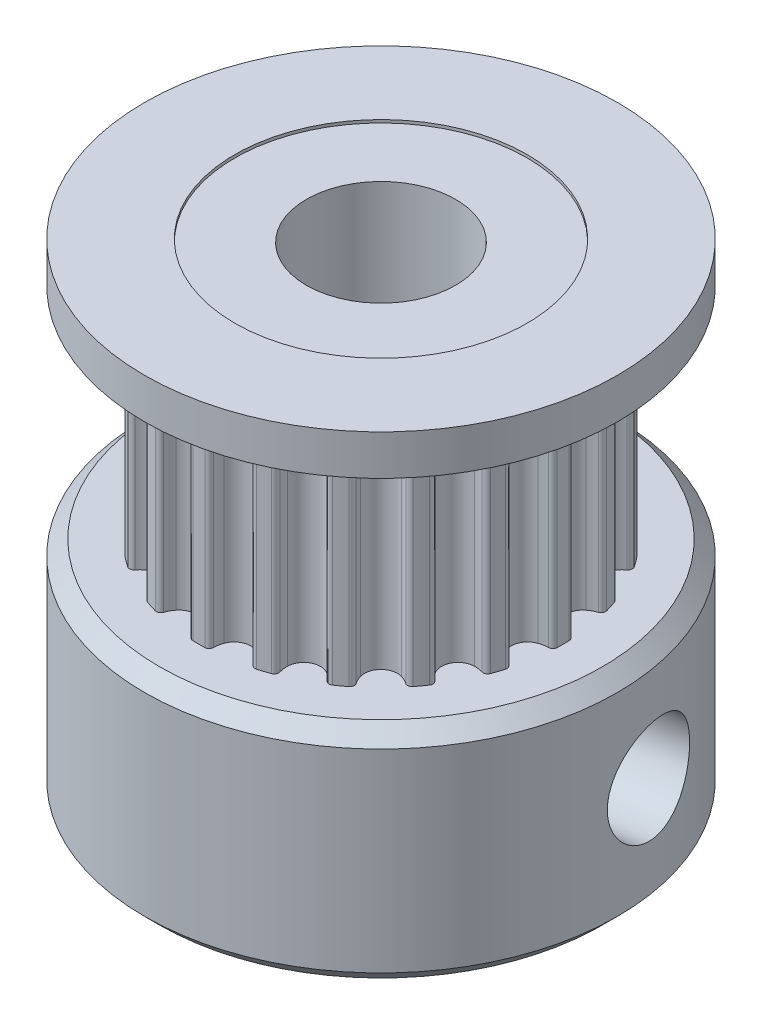
SolidWorks part; units mm, degrees
ref_plane "Front Plane" through (0, 0, 0) normal (0, 0, 1) x (1, 0, 0)
ref_plane "Top Plane" through (0, 0, 0) normal (0, 1, 0) x (1, 0, 0)
ref_plane "Right Plane" through (0, 0, 0) normal (1, 0, 0) x (0, 0, -1)
sketch "Sketch1" plane through (0, 0, 0) normal (0, 1, 0) x (1, 0, 0)
  circle A0 centre (0, 0) radius 6.3662
  dimension "D1" = 12.7324
extrude "Boss-Extrude1" add sketch "Sketch1" along normal mid plane 7.36
sketch "Sketch2" plane through (0, 0, 0) normal (0, 1, 0) x (1, 0, 0)
  line L0 (0, 0) -> (0, 6.1122) construction
  line L1 (0, 0) -> (0.9257, 5.8443) construction
  line L2 (0, 6.1122) -> (0, 6.3662)
  line L3 (0.9257, 5.8443) -> (0.9959, 6.2878) construction
  line L4 (0.9959, 6.2878) -> (1.3888, 6.2129) construction
  line L5 (1.3888, 6.2129) -> (1.3462, 5.9897) construction
  line L6 (1.8888, 5.813) -> (1.9673, 6.0546)
  arc A1 (0, 6.1122) -> (0.2016, 6.1089) centre (0, 0) cw
  arc A2 (0.2016, 6.1089) -> (0.3466, 5.963) centre (0.1967, 5.959) cw
  arc A3 (0.3466, 5.963) -> (0.4011, 5.663) centre (1.3462, 5.9897) ccw
  arc A4 (0.4011, 5.663) -> (1.3685, 5.5098) centre (0.9257, 5.8443) ccw
  circle A5 centre (0, 0) radius 6.3662 construction
  arc A6 (0, 6.3662) -> (1.9673, 6.0546) centre (0, 0) cw
  arc A7 (1.513, 5.7782) -> (1.3685, 5.5098) centre (0.5706, 6.1126) cw
  arc A8 (1.696, 5.8722) -> (1.513, 5.7782) centre (1.6544, 5.7281) ccw
  arc A9 (1.8888, 5.813) -> (1.696, 5.8722) centre (0, 0) ccw
  dimension "D2" = 0.15
  dimension "D3" = 1
  dimension "D4" = 0.555
  dimension "D1" = 9
  dimension "D5" = 0.254
  dimension "D6" = 0.4
  dimension "D7" = 1.004
extrude "Cut-Extrude1" cut sketch "Sketch2" against normal through all both and the other way through all
pattern_circular "CirPattern1" count 20 over 360 about axis through (0, 3.68, 0) along (0, -1, 0) of "Cut-Extrude1"
sketch "Sketch3" plane through (0, 0, 0) normal (0, 1, 0) x (1, 0, 0)
  circle A0 centre (0, 0) radius 7.925
  dimension "15.85" = 15.85
extrude "Boss-Extrude2" add sketch "Sketch3" along normal blind 1.35 from surface starting at face at (0, 3.68, 0)
extrude "Boss-Extrude3" add sketch "Sketch3<2>" against normal blind 7.5 from surface starting at face at (0, -3.68, 0)
sketch "Sketch3<2>" plane through (0, 0, 0) normal (0, 1, 0) x (1, 0, 0) same geometry as "Sketch3"
sketch "Sketch4" plane through (0, 0, 0) normal (0, 1, 0) x (1, 0, 0)
  circle A0 centre (0, 0) radius 2.5
  dimension "D1" = 5
extrude "Cut-Extrude2" cut sketch "Sketch4" against normal through all both and the other way through all
sketch "Sketch5" plane through (0, 5.03, 0) normal (0, 1, 0) x (1, 0, 0)
  circle A0 centre (0, 0) radius 4.9
  dimension "D1" = 9.8
extrude "Cut-Extrude3" cut sketch "Sketch5" against normal blind 0.1
ref_plane "Plane1" through (0, -3.075, 0) normal (0, 1, 0) x (1, 0, 0)
mirror "Mirror1" about plane through (0, -3.075, 0) normal (0, 1, 0) of "Cut-Extrude3"
chamfer "Chamfer1" distance 0.5 angle 45 2 edges at (0, -11.18, 7.925) (0, -3.68, 7.925)
sketch "Sketch6" plane through (0, 0, 0) normal (0, 0, 1) x (1, 0, 0)
  line L0 (7.925, -10.68) -> (7.925, -4.18) construction
  line L1 (7.925, -10.68) -> (7.925, -4.18)
  circle A0 centre (0, -7.43) radius 1.7
  point P7 (7.925, -7.43)
  dimension "D1" = 3.4
extrude "Cut-Extrude4" cut sketch "Sketch6" against normal through all contours A0 region at (0, -7.43, 0)
pattern_circular "CirPattern2" count 2 every 80 about axis through (0, -4.18, 0) along (0, -1, 0) of "Cut-Extrude4"
equation "\"n\"= 20"
equation "\"p\"= 2mm"
equation "\"pd\"= ( \"n\" * \"p\" ) / pi"
equation "\"D1@Sketch1\"=\"pd\""
equation "\"D1@Sketch2\"=180/\"n\""
equation "\"D1@CirPattern1\"=\"n\""
